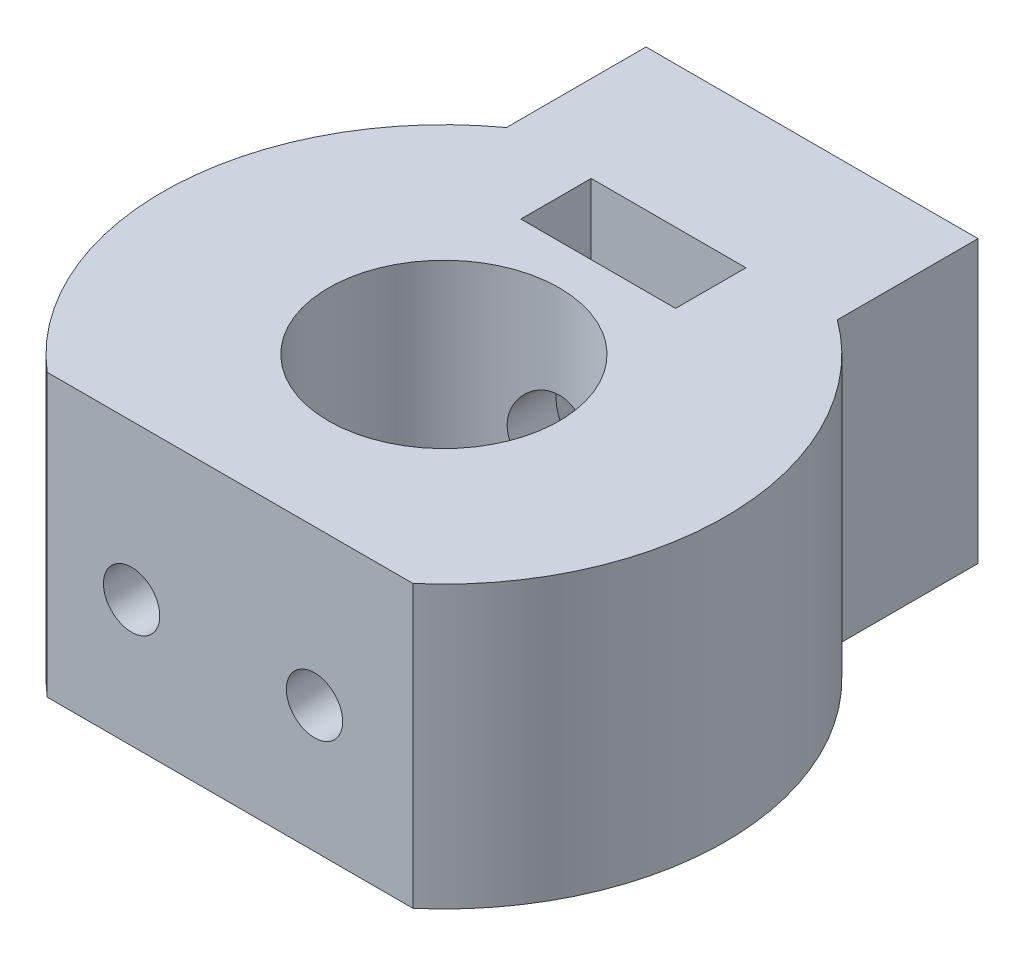
SolidWorks part; units mm, degrees
ref_plane "前视基准面" through (0, 0, 0) normal (0, 0, 1) x (1, 0, 0)
ref_plane "上视基准面" through (0, 0, 0) normal (0, 1, 0) x (1, 0, 0)
ref_plane "右视基准面" through (0, 0, 0) normal (1, 0, 0) x (0, 0, -1)
sketch "草图1" plane through (0, 0, 0) normal (0, 1, 0) x (1, 0, 0)
  circle A0 centre (0, 0) radius 10
  circle A1 centre (0, 0) radius 4.1
  dimension "D1" = 20
  dimension "D2" = 8.2
extrude "凸台-拉伸1" add sketch "草图1" along normal blind 10
sketch "草图2" plane through (0, 10, 0) normal (0, 1, 0) x (1, 0, 0)
  line L0 (-6.5, -7.5993) -> (6.5, -7.5993)
  circle A0 centre (0, 0) radius 10 construction
  arc A1 (-6.5, -7.5993) -> (6.5, -7.5993) centre (0, 0) ccw
  dimension "D1" = 13
extrude "切除-拉伸1" cut sketch "草图2" against normal through all
sketch "草图3" plane through (0, 0, 7.5993) normal (0, 0, 1) x (1, 0, 0)
  line L0 (6.5, 0) -> (-6.5, 0) construction
  line L1 (6.5, 0) -> (6.5, 10) construction
  circle A0 centre (-3.5, 4.5) radius 1
  circle A1 centre (3, 4.5) radius 1
  dimension "D2" = 2
  dimension "D3" = 2
  dimension "D4" = 4.5
  dimension "D5" = 3.5
  dimension "D1" = 6.5
extrude "切除-拉伸2" cut sketch "草图3" against normal blind 7
ref_plane "基准面1" through (0, 0, -2.4007) normal (0, 0, 1) x (1, 0, 0)
sketch "草图4" plane through (0, 0, -2.4007) normal (0, 0, 1) x (1, 0, 0)
  circle A0 centre (0, 5.1488) radius 1.55
  dimension "D1" = 3.1
extrude "切除-拉伸3" cut sketch "草图4" against normal blind 11
sketch "草图5" plane through (0, 10, 0) normal (0, 1, 0) x (1, 0, 0)
  line L1 (-2.7991, 8.0328) -> (2.7009, 8.0328)
  line L2 (-2.7991, 8.0328) -> (-2.7991, 5.5328)
  line L3 (-2.7991, 5.5328) -> (2.7009, 5.5328)
  line L4 (2.7009, 8.0328) -> (2.7009, 5.5328)
  dimension "D1" = 2.5
  dimension "D2" = 5.5
extrude "切除-拉伸4" cut sketch "草图5" against normal blind 8
sketch "草图6" plane through (0, 10, 0) normal (0, 1, 0) x (1, 0, 0)
  line L1 (-5.8716, 13.0542) -> (5.9271, 13.0542)
  line L2 (-5.8716, 13.0542) -> (-5.8716, 8.0542)
  line L3 (-5.8716, 8.0542) -> (5.9271, 8.0542)
  line L4 (5.9271, 13.0542) -> (5.9271, 8.0542)
  arc A0 (6.5, -7.5993) -> (-6.5, -7.5993) centre (0, 0) ccw construction
  dimension "D1" = 5
extrude "凸台-拉伸2" add sketch "草图6" against normal up to surface (10 mm away) up to face at (0, 0, -1.2003)
sketch "草图7" plane through (0, 0, -8.0542) normal (0, 0, 1) x (1, 0, 0)
  circle A0 centre (0, 5.1488) radius 1.55 construction
  circle A1 centre (0, 5.1488) radius 1.55
extrude "切除-拉伸5" cut sketch "草图7" against normal blind 9
